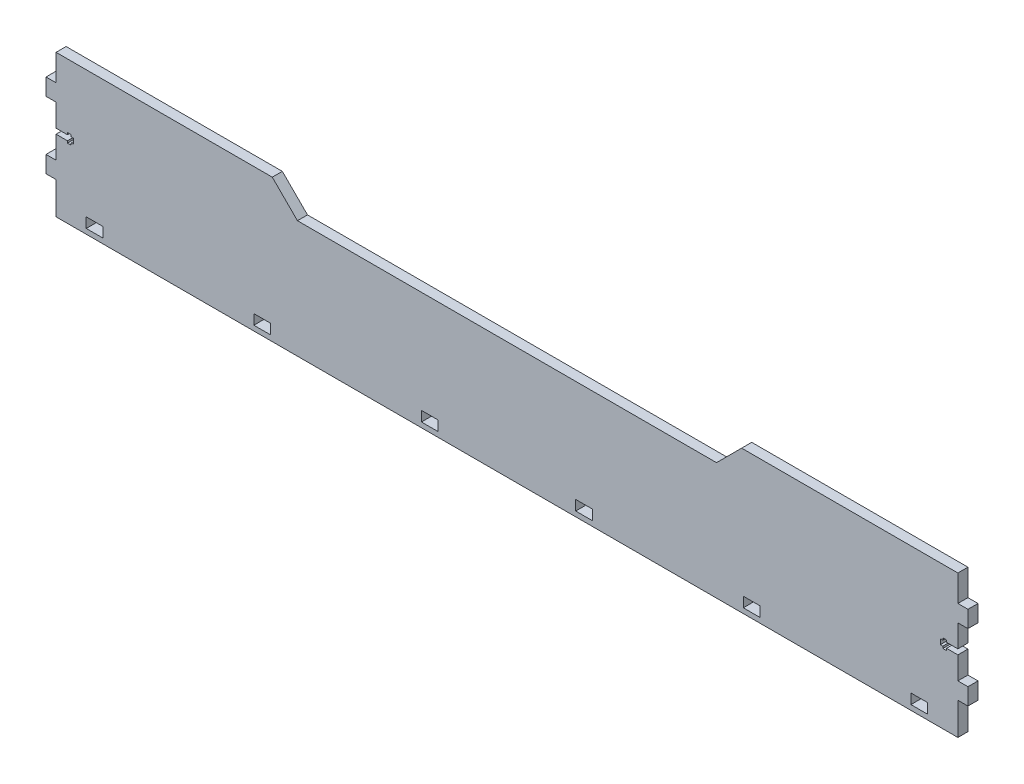
SolidWorks part; units mm, degrees
material "Клен"
ref_plane "Спереди" through (0, 0, 0) normal (0, 0, 1) x (1, 0, 0)
ref_plane "Сверху" through (0, 0, 0) normal (0, 1, 0) x (1, 0, 0)
ref_plane "Справа" through (0, 0, 0) normal (1, 0, 0) x (0, 0, -1)
sketch "Эскиз1" plane through (0, 0, 0) normal (0, 0, 1) x (1, 0, 0)
  line L0 (-241.6648, -61.8411) -> (389.5038, -61.8411) construction
  line L1 (-177.5862, 18.1589) -> (-48.5862, 18.1589)
  line L2 (-177.5862, 18.1589) -> (-177.5862, 2.4089)
  line L3 (-177.5862, -66.8411) -> (360.4138, -66.8411)
  line L4 (360.4138, 18.1589) -> (360.4138, 2.4089)
  line L9 (216.4138, 3.1589) -> (231.4138, 18.1589)
  line L12 (-33.5862, 3.1589) -> (216.4138, 3.1589)
  line L14 (-201.809, -22.5911) -> (-94.0246, -22.5911) construction
  line L15 (-164.6015, 57.6307) -> (-164.6015, -109.5576) construction
  line L16 (-33.5862, 3.1589) -> (-48.5862, 18.1589)
  line L17 (91.4138, 3.1589) -> (91.4138, -97.1189) construction
  line L18 (231.4138, 18.1589) -> (360.4138, 18.1589)
  line L19 (-177.5862, -7.5911) -> (-177.5862, -21.0411)
  line L20 (-177.5862, 2.4089) -> (-183.5862, 2.4089)
  line L22 (-177.5862, -7.5911) -> (-183.5862, -7.5911)
  line L23 (-183.5862, 2.4089) -> (-183.5862, -7.5911)
  line L24 (-183.5862, -47.5911) -> (-183.5862, -37.5911)
  line L25 (-177.5862, -37.5911) -> (-183.5862, -37.5911)
  line L26 (-177.5862, -47.5911) -> (-183.5862, -47.5911)
  line L27 (-177.5862, -47.5911) -> (-177.5862, -66.8411)
  line L28 (360.4138, -47.5911) -> (366.4138, -47.5911)
  line L29 (360.4138, -37.5911) -> (366.4138, -37.5911)
  line L30 (366.4138, -47.5911) -> (366.4138, -37.5911)
  line L31 (366.4138, 2.4089) -> (366.4138, -7.5911)
  line L32 (360.4138, -7.5911) -> (366.4138, -7.5911)
  line L33 (360.4138, 2.4089) -> (366.4138, 2.4089)
  line L34 (360.4138, -7.5911) -> (360.4138, -21.0411)
  line L35 (360.4138, -47.5911) -> (360.4138, -66.8411)
  line L36 (-206.0693, -63.8411) -> (371.2193, -63.8411) construction
  line L37 (-59.5862, -63.8411) -> (-59.5862, -57.8411)
  line L38 (-159.5862, -63.8411) -> (-149.5862, -63.8411)
  line L39 (-159.5862, -63.8411) -> (-159.5862, -57.8411)
  line L40 (-159.5862, -57.8411) -> (-149.5862, -57.8411)
  line L41 (-149.5862, -63.8411) -> (-149.5862, -57.8411)
  line L42 (-59.5862, -63.8411) -> (-49.5862, -63.8411)
  line L43 (-49.5862, -63.8411) -> (-49.5862, -57.8411)
  line L44 (-59.5862, -57.8411) -> (-49.5862, -57.8411)
  line L45 (40.4138, -63.8411) -> (40.4138, -57.8411)
  line L46 (40.4138, -63.8411) -> (50.4138, -63.8411)
  line L47 (50.4138, -63.8411) -> (50.4138, -57.8411)
  line L48 (40.4138, -57.8411) -> (50.4138, -57.8411)
  line L49 (-178.822, -22.5911) -> (-176.4935, -22.5911) construction
  line L50 (-177.5862, -19.8411) -> (-177.5862, -25.3411) construction
  line L51 (-177.5862, -21.0411) -> (-170.7862, -21.0411)
  line L52 (-168.5862, -25.3411) -> (-170.7862, -25.3411)
  line L53 (-167.0862, -21.0411) -> (-167.0862, -24.1411)
  line L54 (-170.7862, -25.3411) -> (-170.7862, -24.1411)
  line L55 (-168.5862, -19.8411) -> (-168.5862, -21.0411)
  line L56 (-168.5862, -24.1411) -> (-168.5862, -25.3411)
  line L57 (-170.7862, -21.0411) -> (-170.7862, -19.8411)
  line L58 (-170.7862, -19.8411) -> (-168.5862, -19.8411)
  line L59 (-168.5862, -21.0411) -> (-167.0862, -21.0411)
  line L60 (-170.7862, -24.1411) -> (-177.5862, -24.1411)
  line L61 (-167.0862, -24.1411) -> (-168.5862, -24.1411)
  line L62 (-177.5862, -24.1411) -> (-177.5862, -37.5911)
  line L63 (360.4138, -19.8411) -> (360.4138, -25.3411) construction
  line L64 (361.6495, -22.5911) -> (359.321, -22.5911) construction
  line L65 (349.9138, -24.1411) -> (351.4138, -24.1411)
  line L66 (353.6138, -24.1411) -> (360.4138, -24.1411)
  line L67 (351.4138, -21.0411) -> (349.9138, -21.0411)
  line L68 (353.6138, -19.8411) -> (351.4138, -19.8411)
  line L69 (353.6138, -21.0411) -> (353.6138, -19.8411)
  line L70 (351.4138, -24.1411) -> (351.4138, -25.3411)
  line L71 (351.4138, -19.8411) -> (351.4138, -21.0411)
  line L72 (353.6138, -25.3411) -> (353.6138, -24.1411)
  line L73 (349.9138, -21.0411) -> (349.9138, -24.1411)
  line L74 (351.4138, -25.3411) -> (353.6138, -25.3411)
  line L75 (360.4138, -21.0411) -> (353.6138, -21.0411)
  line L76 (360.4138, -24.1411) -> (360.4138, -37.5911)
  line L77 (142.4138, -63.8411) -> (132.4138, -63.8411)
  line L78 (132.4138, -63.8411) -> (132.4138, -57.8411)
  line L79 (142.4138, -57.8411) -> (132.4138, -57.8411)
  line L80 (142.4138, -63.8411) -> (142.4138, -57.8411)
  line L81 (242.4138, -63.8411) -> (232.4138, -63.8411)
  line L82 (232.4138, -63.8411) -> (232.4138, -57.8411)
  line L83 (242.4138, -57.8411) -> (232.4138, -57.8411)
  line L84 (242.4138, -63.8411) -> (242.4138, -57.8411)
  line L85 (342.4138, -57.8411) -> (332.4138, -57.8411)
  line L86 (332.4138, -63.8411) -> (332.4138, -57.8411)
  line L87 (342.4138, -63.8411) -> (332.4138, -63.8411)
  line L88 (342.4138, -63.8411) -> (342.4138, -57.8411)
  point P4 (94.6325, 20.7187)
  dimension "D5" = 6
  dimension "D1" = 538
  dimension "D2" = 85
  dimension "D3" = 5
  dimension "D4" = 39.25
  dimension "D6" = 15
  dimension "D7" = 269
  dimension "D8" = 10
  dimension "D9" = 3
  dimension "D10" = 10
  dimension "D11" = 6
  dimension "D13" = 18
  dimension "D12" = 3
extrude "Бобышка-Вытянуть1" add sketch "Эскиз1" along normal blind 6
